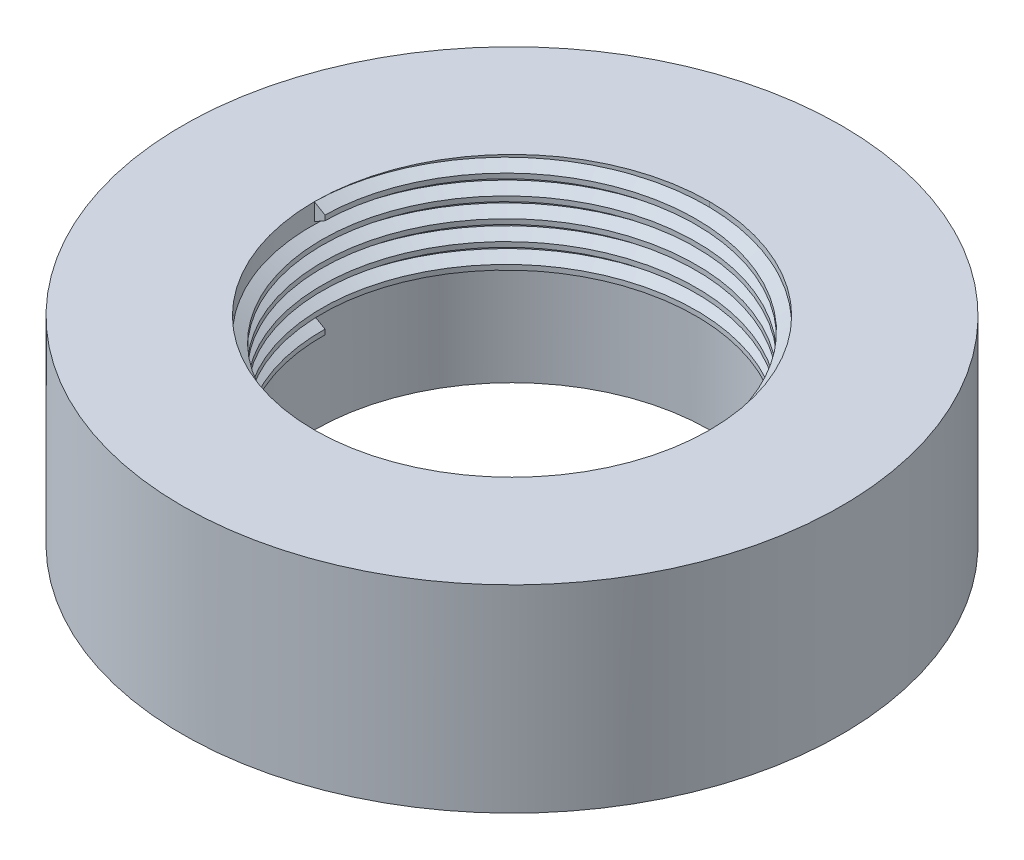
SolidWorks part; units mm, degrees
ref_plane "Front Plane" through (0, 0, 0) normal (0, 0, 1) x (1, 0, 0)
ref_plane "Top Plane" through (0, 0, 0) normal (0, 1, 0) x (1, 0, 0)
ref_plane "Right Plane" through (0, 0, 0) normal (1, 0, 0) x (0, 0, -1)
sketch "Sketch1" plane through (0, 0, 0) normal (0, 1, 0) x (1, 0, 0)
  circle A0 centre (0, 0) radius 112.5
  dimension "D1" = 225
extrude "Boss-Extrude1" add sketch "Sketch1" along normal blind 65
shell "Shell1" thickness 5 removed face at (0, 65, 112.5)
sketch "Sketch2" plane through (0, 5, 0) normal (0, 1, 0) x (1, 0, 0)
  circle A0 centre (0, 0) radius 25
  dimension "D1" = 50
extrude "Boss-Extrude2" add sketch "Sketch2" along normal up to surface (60 mm away) up to face at (0, 65, 107.5)
shell "Shell2" thickness 10 removed face at (0, 65, 25)
sketch "Sketch3" plane through (0, 0, 0) normal (0, 0, 1) x (1, 0, 0)
  line L0 (0, 0) -> (0, 65) construction
  line L1 (112.5, 65) -> (-112.5, 65) construction
  circle A0 centre (0, 32.5) radius 1.25
  dimension "D1" = 2.5
extrude "Cut-Extrude1" cut sketch "Sketch3" against normal through all
sketch "Sketch6" plane through (0, 65, 0) normal (0, 1, 0) x (1, 0, 0)
  circle A0 centre (0, 0) radius 107.5
  circle A1 centre (0, 0) radius 112.5
extrude "Boss-Extrude3" add sketch "Sketch6" along normal blind 81.25
sketch "Sketch7" plane through (0, 0, 0) normal (1, 0, 0) x (0, 0, -1)
  line L0 (25, 65) -> (112.5, 65) construction
  line L1 (112.5, 33.75) -> (112.5, 146.25) construction
  line L2 (112.5, 146.25) -> (-112.5, 146.25) construction
  line L3 (112.5, 65) -> (-112.5, 65)
  line L4 (112.5, 65) -> (112.5, 146.25)
  line L5 (112.5, 146.25) -> (-112.5, 146.25)
  line L6 (-112.5, 65) -> (-112.5, 146.25)
extrude "Cut-Extrude2" cut sketch "Sketch7" against normal through all
thread "Thread1" pitch 1.5 method extrude profile "Thread Profile1" start angle 0, offset 0, length 7.5, pitch 1.5, diameter 30
ref_plane "Plane1" through (-15, 65, 0) normal (0, 0, 1) x (-1, 0, 0)
sketch "Thread Profile1" plane through (-15, 65, 0) normal (0, 0, 1) x (-1, 0, 0)
  line L0 (0, 0) -> (0, 1.5) construction
  line L11 (0, 0) -> (0, 1.3125)
  line L12 (0, 1.3125) -> (-0.8119, 0.8437)
  line L13 (-0.8119, 0.8437) -> (-0.8119, 0.4687)
  line L15 (-0.8119, 0.4687) -> (0, 0)
  line L17 (-0.8119, 0.6562) -> (0, 0.6562) construction
  point P2 (0, 0)
  dimension "Pitch" = 1.5
  dimension "Profile_Angle" = 60
  dimension "Profile_Land" = 0.375
  dimension "Profile_Height" = 0.8119
sketch "Sketch15" plane through (0, 0, 0) normal (0, 0, 1) x (1, 0, 0)
  line L0 (0, 65) -> (-112.5, 65) construction
  line L1 (10, 85) -> (20, 85)
  line L2 (10, 85) -> (10, 90)
  line L3 (10, 90) -> (20, 90)
  line L4 (20, 85) -> (20, 90)
  line L5 (10, 121.25) -> (20, 121.25)
  line L6 (10, 121.25) -> (10, 126.25)
  line L7 (10, 126.25) -> (20, 126.25)
  line L8 (20, 121.25) -> (20, 126.25)
  line L9 (112.5, 146.25) -> (0, 146.25) construction
  line L10 (0, 65) -> (0, 146.25) construction
  dimension "D1" = 10
  dimension "D2" = 10
  dimension "D3" = 5
  dimension "D4" = 5
  dimension "D5" = 20
  dimension "D6" = 20
  dimension "D7" = 10
  dimension "D8" = 10
extrude "Cut-Extrude3" cut sketch "Sketch15" against normal through all
sketch "Sketch16" plane through (0, 0, 0) normal (0, -1, 0) x (1, 0, 0)
  circle A0 centre (0, 0) radius 27.5
  dimension "D1" = 55
extrude "Cut-Extrude4" cut sketch "Sketch16" against normal through all both and the other way through all flip side to cut
sketch "Sketch17" plane through (0, 0, 0) normal (0, -1, 0) x (1, 0, 0)
  circle A0 centre (0, 0) radius 27.5
extrude "Cut-Extrude5" cut sketch "Sketch17" against normal blind 50
